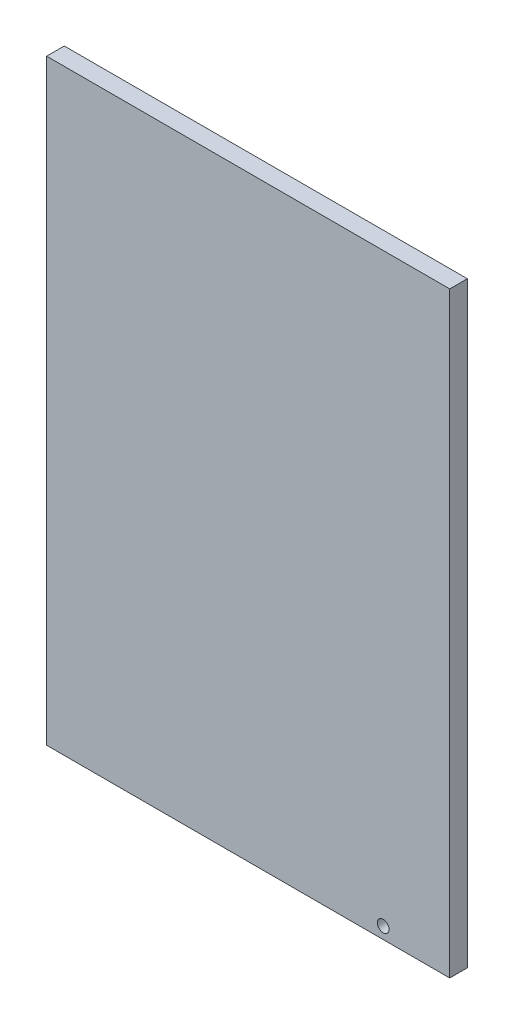
SolidWorks part; units mm, degrees
ref_plane "Front Plane" through (0, 0, 0) normal (0, 0, 1) x (1, 0, 0)
ref_plane "Top Plane" through (0, 0, 0) normal (0, 1, 0) x (1, 0, 0)
ref_plane "Right Plane" through (0, 0, 0) normal (1, 0, 0) x (0, 0, -1)
sketch "Sketch1" plane through (0, 0, 0) normal (0, 0, 1) x (1, 0, 0)
  line L1 (-103, -152.5) -> (103, -152.5)
  line L2 (-103, -152.5) -> (-103, 152.5)
  line L3 (-103, 152.5) -> (103, 152.5)
  line L4 (103, -152.5) -> (103, 152.5)
  line L5 (-103, -152.5) -> (103, 152.5) construction
  line L6 (-103, 152.5) -> (103, -152.5) construction
  point P0 (0, 0)
  dimension "D1" = 206
  dimension "D2" = 305
extrude "Boss-Extrude1" add sketch "Sketch1" along normal blind 9
sketch "Sketch2" plane through (0, 0, 9) normal (0, 0, 1) x (1, 0, 0)
  line L0 (103, -152.5) -> (103, 152.5) construction
  line L1 (-103, -152.5) -> (103, -152.5) construction
  circle A0 centre (69, -146.5) radius 3
  dimension "D1" = 6
  dimension "D2" = 34
  dimension "D3" = 6
extrude "Cut-Extrude1" cut sketch "Sketch2" against normal through all
sketch "Sketch3" [suppressed] plane through (0, 0, 0) normal (0, 0, -1) x (-1, 0, 0)
  line L0 (-120.2594, -152.5) -> (119.7406, -152.5) construction
  line L2 (-90.2594, -139.5) -> (-30.2594, -139.5) construction
  line L3 (-30.2594, -139.5) -> (29.7406, -139.5) construction
  line L4 (29.7406, -139.5) -> (89.7406, -139.5) construction
  circle A0 centre (-90.2594, -139.5) radius 4.75
  circle A1 centre (-30.2594, -139.5) radius 5.5875
  circle A2 centre (29.7406, -139.5) radius 5.5875
  circle A3 centre (89.7406, -139.5) radius 4.75
  point P3 (-0.2594, -152.5)
  dimension "D2" = 9.5
  dimension "D7" = 11.175
  dimension "D1" = 240
  dimension "D3" = 13
  dimension "D4" = 30
  dimension "D5" = 60
  dimension "D6" = 60
  dimension "60" = 60
extrude "Cut-Extrude2" [suppressed] cut sketch "Sketch3" against normal through all
equation "\"PCLength\"= 316mm'Length across I/O from PS to GPU"
equation "\"PCWidth\"= 242mm'Distance of longest part parallel to GPU(ussually GPU)"
equation "\"PCHeight\"= 178mm'Tallest point with mobo laying flat"
equation "\"WallThickness\"= 9mm'Thickness of each outer tank wall"
equation "\"ThermoBarrierThickness\"= 3mm'Thickness of barrier between hot side and cold side"
equation "\"HotSideGap\"= 25mm'Space in the hot side for a pump"
equation "\"PCClearance\"= 30mm'Clearance from top of tank to top of PC"
equation "\"RadiatorHeight\"= 275mm'Final Height from ground of radiators"
equation "\"D1@Sketch1\"=\"PCHeight\" + \"ThermoBarrierThickness\" + \"HotSideGap\""
equation "\"D2@Sketch1\"=\"RadiatorHeight\" + \"PCClearance\""
equation "\"D1@Boss-Extrude1\"=\"WallThickness\""
equation "\"D2@Sketch2\"=\"HotSideGap\" + \"ThermoBarrierThickness\" + 6"
